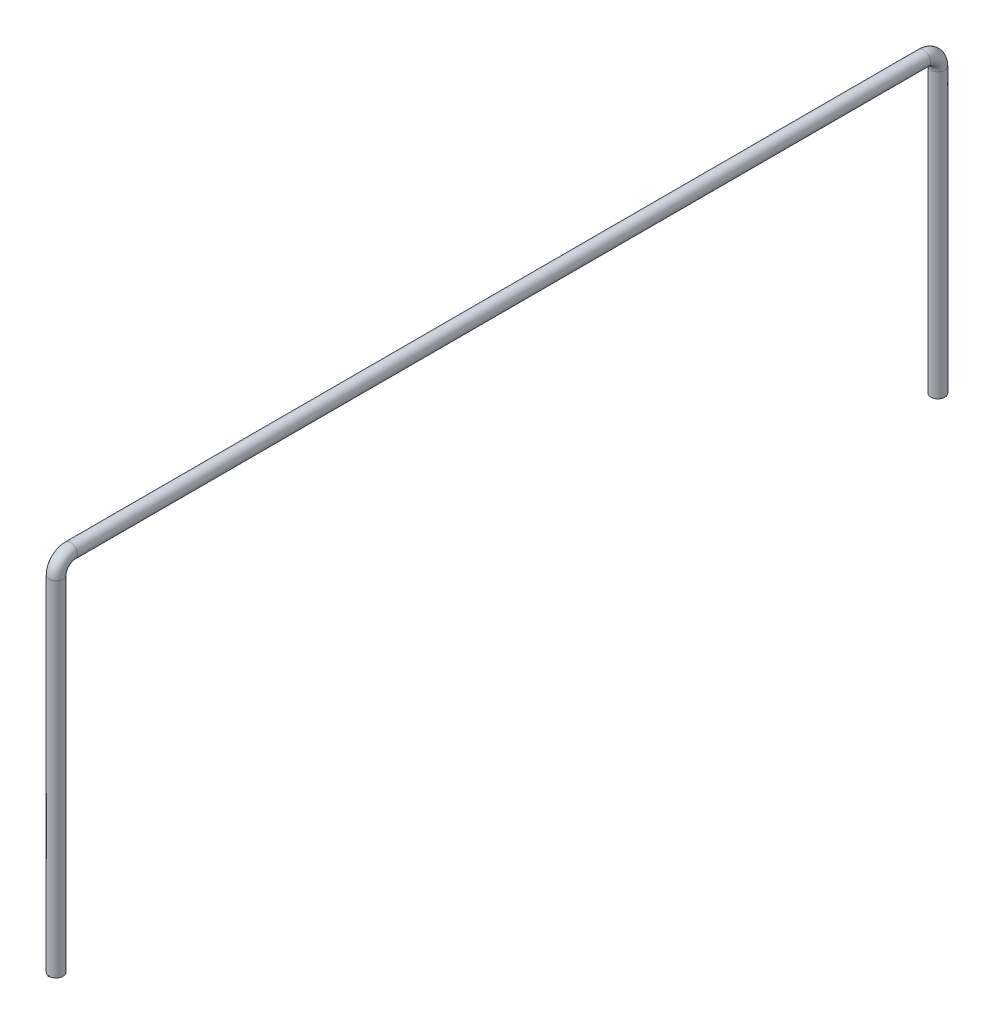
SolidWorks part; units mm, degrees
ref_plane "Alzado" through (0, 0, 0) normal (0, 0, 1) x (1, 0, 0)
ref_plane "Planta" through (0, 0, 0) normal (0, 1, 0) x (1, 0, 0)
ref_plane "Vista lateral" through (0, 0, 0) normal (1, 0, 0) x (0, 0, -1)
sketch "Croquis1" plane through (0, 0, 0) normal (0, 1, 0) x (1, 0, 0)
  circle A0 centre (0, 0) radius 12.7
  dimension "D1" = 25.4
extrude "Saliente-Extruir1" add sketch "Croquis1" along normal blind 400
sketch3d "Croquis3D1"
  line L0 (0, 400, 0) -> (0, 624, 0)
  line L1 (0, 400, 0) -> (0, 0, 0) construction
  line L2 (0, 650, -26) -> (0, 650, -1574)
  line L3 (0, 624, -1600) -> (0, 110, -1600)
  arc A0 (0, 650, -1574) -> (0, 624, -1600) centre (0, 624, -1574) ccw
  arc A1 (0, 624, 0) -> (0, 650, -26) centre (0, 624, -26) ccw
  point P8 (0, 650, -1600)
  point P9 (-26, 624, -1574)
  point P12 (0, 650, 0)
  point P13 (-26, 624, -26)
  dimension "D4" = 26
  dimension "D1" = 250
  dimension "D2" = 1600
  dimension "D3" = 540
sketch "Croquis2" plane through (0, 400, 0) normal (0, 1, 0) x (1, 0, 0)
  circle A0 centre (0, 0) radius 12.7
  dimension "D1" = 25.4
sweep "Barrer1" add profiles "Croquis2" path "Croquis3D1"
sketch "Croquis3" plane through (0, 0, 0) normal (0, -1, 0) x (1, 0, 0)
  line L1 (-0.9329, 11.9355) -> (0.9329, 11.9355)
  line L2 (-0.9329, 11.9355) -> (-0.9329, 13.4645)
  line L3 (-0.9329, 13.4645) -> (0.9329, 13.4645)
  line L4 (0.9329, 11.9355) -> (0.9329, 13.4645)
  line L5 (-0.9329, 11.9355) -> (0.9329, 13.4645) construction
  line L6 (-0.9329, 13.4645) -> (0.9329, 11.9355) construction
  circle A0 centre (0, 0) radius 12.7 construction
  point P0 (0, 12.7)
extrude "Saliente-Extruir2" add sketch "Croquis3" against normal blind 1
